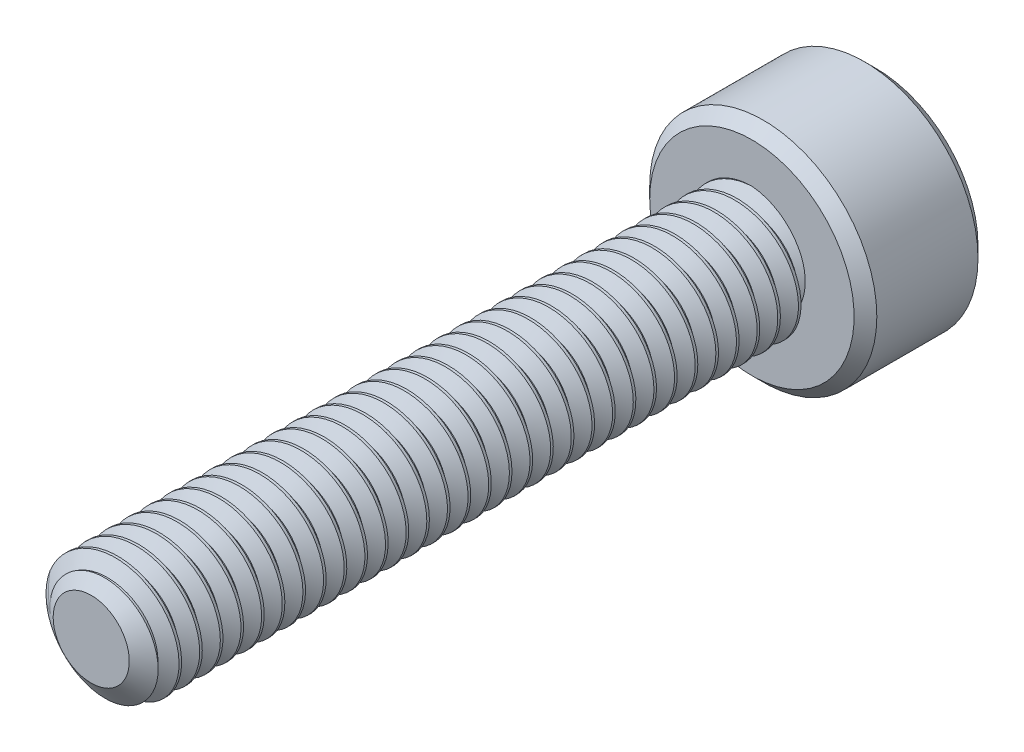
SolidWorks part; units mm, degrees
ref_plane "Front Plane" through (0, 0, 0) normal (0, 0, 1) x (1, 0, 0)
ref_plane "Top Plane" through (0, 0, 0) normal (0, 1, 0) x (1, 0, 0)
ref_plane "Right Plane" through (0, 0, 0) normal (1, 0, 0) x (0, 0, -1)
sketch "Sketch1" plane through (0, 0, 0) normal (0, 0, 1) x (1, 0, 0)
  circle A0 centre (0, 0) radius 1.5
  dimension "OD" = 3
extrude "Extrude1" add sketch "Sketch1" against normal blind 16
sketch "Sketch2" plane through (0, 0, 0) normal (0, 0, 1) x (1, 0, 0)
  circle A0 centre (0, 0) radius 1.5 construction
  circle A1 centre (0, 0) radius 1.5
curve "Helix/Spiral1" pitch 0.5 height 16.5 turns 33 parameters "pitch"=0.5
sketch "Sketch3" plane through (0, 0, 0) normal (1, 0, 0) x (0, 0, -1)
  line L0 (-0.4375, 1.5) -> (-0.25, 1.1752)
  line L1 (-0.25, 1.1752) -> (-0.1875, 1.1752)
  line L2 (-0.1875, 1.1752) -> (0, 1.5)
  line L3 (-0.4375, 1.5) -> (0, 1.5)
  line L4 (-0.2187, 1.5) -> (-0.2187, 1.1752) construction
  line L5 (-0.3438, 1.3376) -> (-0.0937, 1.3376) construction
  line L6 (0, 1.5) -> (0, -1.5) construction
  dimension "D1" = 0.0625
  dimension "D2" = 0.25
  dimension "D3" = 60
sweep "Cut-Sweep1" cut profiles "Sketch3" path "Helix/Spiral1"
sketch "Sketch4" plane through (0, 0, 0) normal (1, 0, 0) x (0, 0, -1)
  line L0 (0.4053, 1.5) -> (0, 0.9212)
  line L1 (0, 0.9212) -> (0, 1.5)
  line L2 (0.4053, 1.5) -> (0, 1.5)
  line L3 (-0.4375, 1.5) -> (0, 1.5) construction
  line L4 (0, 0) -> (7.0209, 0) construction
  dimension "D1" = 55
  dimension "D2" = 0.254
revolve "Cut-Revolve1" cut sketch "Sketch4" angle 360 about L4
sketch "Sketch6" plane through (0, 0, -16) normal (0, 0, -1) x (-1, 0, 0)
  circle A0 centre (0, 0) radius 2.75
  dimension "head dia" = 5.5
extrude "Extrude2" add sketch "Sketch6" along normal blind 3
sketch "Sketch7" plane through (0, 0, -19) normal (0, 0, -1) x (-1, 0, 0)
  line L1 (0, 1.4434) -> (-1.25, 0.7217)
  line L2 (-1.25, 0.7217) -> (-1.25, -0.7217)
  line L3 (-1.25, -0.7217) -> (0, -1.4434)
  line L4 (0, -1.4434) -> (1.25, -0.7217)
  line L5 (1.25, -0.7217) -> (1.25, 0.7217)
  line L6 (1.25, 0.7217) -> (0, 1.4434)
  circle A0 centre (0, 0) radius 1.25 construction
  dimension "hex dia" = 2.5
extrude "Cut-Extrude1" cut sketch "Sketch7" against normal blind 1.875
sketch "Sketch8" plane through (0, 0, -19) normal (0, 0, -1) x (-1, 0, 0)
  circle A0 centre (0, 0) radius 1.4434
extrude "Cut-Extrude2" cut sketch "Sketch8" against normal through all draft 45
chamfer "Chamfer1" distance 0.275 angle 45 2 edges at (-2.75, 0, -19) (-2.75, 0, -16)
sketch "Sketch9" plane through (0, 0, 0) normal (1, 0, 0) x (0, 0, -1)
  line L0 (0, 1.5) -> (0, -1.5) construction
  line L1 (2.75, 1.5) -> (2.75, -1.5) construction
  dimension "D1" = 2.75
equation "\"D3@Helix/Spiral1\" = \"screw length@Extrude1\"+\"pitch@Helix/Spiral1\""
equation "\"D1@Sketch3\" = \"pitch@Helix/Spiral1\"*.125"
equation "\"D2@Sketch3\" = \"pitch@Helix/Spiral1\"*.5"
equation "\"D1@Cut-Extrude1\" = \"hex dia@Sketch7\"*.75"
equation "\"D1@Chamfer1\" = \"head dia@Sketch6\"*.05"
equation "\"D1@Sketch9\" = \"pitch@Helix/Spiral1\"*5.5"
